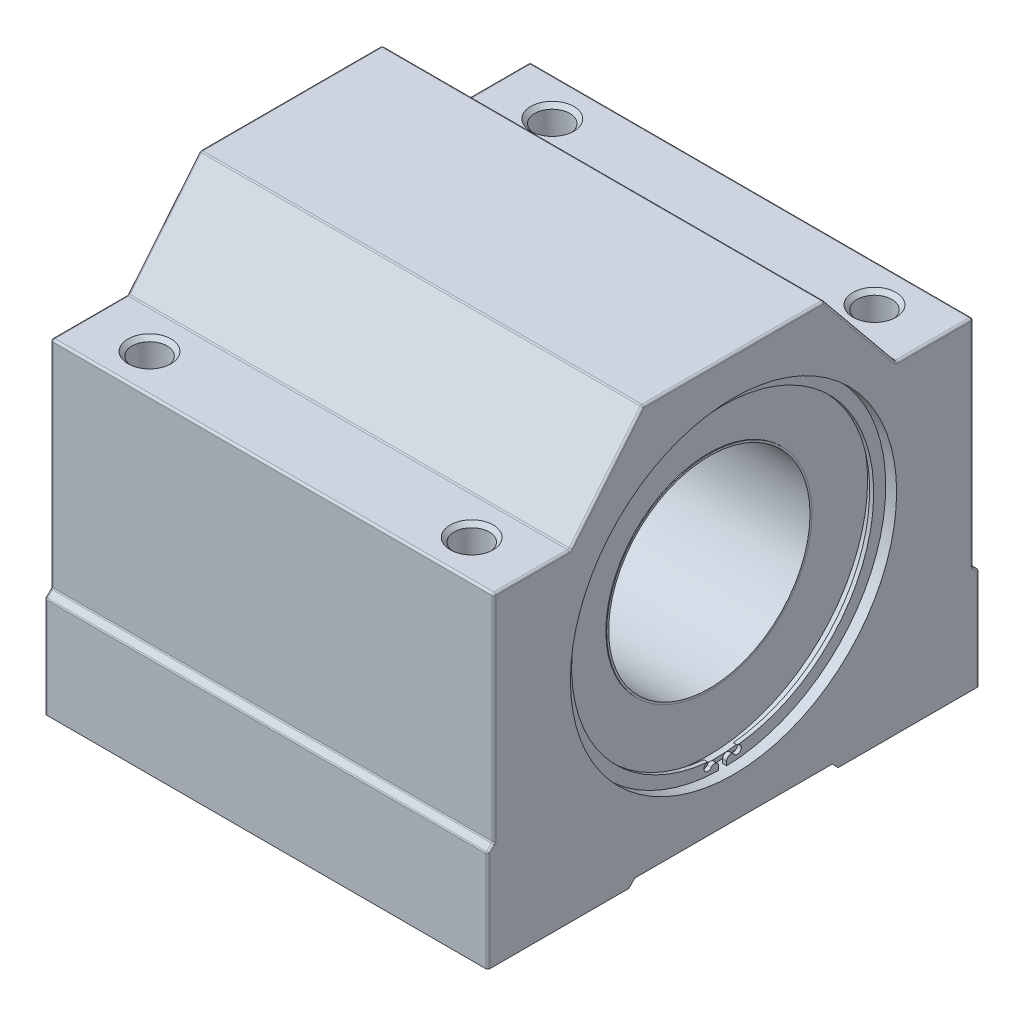
SolidWorks part; units mm, degrees
ref_plane "Front Plane" through (0, 0, 0) normal (0, 0, 1) x (1, 0, 0)
ref_plane "Top Plane" through (0, 0, 0) normal (0, 1, 0) x (1, 0, 0)
ref_plane "Right Plane" through (0, 0, 0) normal (1, 0, 0) x (0, 0, -1)
sketch "Sketch1" plane through (0, 0, 0) normal (1, 0, 0) x (0, 0, -1)
  line L1 (-26, -52) -> (-24.5, -50.5)
  line L2 (-24.5, -50.5) -> (24.5, -50.5)
  line L3 (24.5, -50.5) -> (26, -52)
  line L4 (26, -52) -> (61, -52)
  line L6 (61, -27) -> (59.5, -25.5)
  line L8 (59.5, 28) -> (40.5, 28)
  line L9 (40.5, 28) -> (22.5, 50)
  line L10 (22.5, 50) -> (-22.5, 50)
  line L11 (-22.5, 50) -> (-40.5, 28)
  line L12 (-40.5, 28) -> (-59.5, 28)
  line L15 (-61, -27) -> (-61, -52)
  line L16 (0, -50.5) -> (0, 50) construction
  line L17 (-16.278, 0) -> (14.0247, 0) construction
  line L18 (-61, -52) -> (-26, -52)
  line L19 (61, -27) -> (61, -52)
  line L20 (-59.5, -25.5) -> (-59.5, 28)
  line L21 (59.5, -25.5) -> (59.5, 28)
  line L22 (-50, 28) -> (-50, -52) construction
  line L23 (-50, -52) -> (50, 28) construction
  line L24 (50, 28) -> (50, -52) construction
  line L25 (-61, -27) -> (-59.5, -25.5)
  line L26 (-40.5, 0) -> (40.5, 0) construction
  circle A0 centre (0, 0) radius 40.5
  circle A1 centre (0, 0) radius 39.5
  circle A2 centre (0, 0) radius 25
  point P18 (0, 50)
  dimension "D12" = 50
  dimension "D1" = 122
  dimension "D2" = 80
  dimension "D3" = 52
  dimension "D5" = 102
  dimension "D6" = 100
  dimension "D4" = 25
  dimension "D7" = 1.5
  dimension "D8" = 45
  dimension "D9" = 1.5
  dimension "D10" = 35
  dimension "D11" = 1
extrude "Boss-Extrude1" add sketch "Sketch1" along normal blind 110 contours L25 L15 L18 L1 L2 L3 L4 L19 L6 L21 L8 L9 L10 L11 L12 L20 A0 region at (0, -50.4098, 43.5)
extrude "Extrude-Thin1" add sketch "Sketch1<4>" along normal blind 103.5 from offset 0.5 separate body thin contours A2 thin type one direction wall 0.5
sketch "Sketch1<4>" plane through (0, 0, 0) normal (1, 0, 0) x (0, 0, -1) same geometry as "Sketch1"
extrude "Boss-Extrude2" add sketch "Sketch1<5>" along normal blind 103 from offset 0.8 contours A1 A2 region at (0, 0, 38.3828)
sketch "Sketch1<5>" plane through (0, 0, 0) normal (1, 0, 0) x (0, 0, -1) same geometry as "Sketch1"
extrude "Boss-Extrude3" add sketch "Sketch1<6>" along normal blind 105 from offset 0.3 contours A0 A1 region at (0, 0, 40.3854)
sketch "Sketch1<6>" plane through (0, 0, 0) normal (1, 0, 0) x (0, 0, -1) same geometry as "Sketch1"
ref_plane "Plane1" through (105.3, 0, 0) normal (1, 0, 0) x (0, 0, -1)
sketch "Sketch3" plane through (105.3, 0, 0) normal (1, 0, 0) x (0, 0, -1)
  line L0 (0, 0) -> (0, -50000) construction
  line L1 (-1.0007, -39.4873) -> (-1.0261, -40.487)
  line L2 (1.0007, -39.4873) -> (1.0261, -40.487)
  circle A0 centre (0, 0) radius 40.5 construction
  arc A1 (1.0261, -40.487) -> (-1.0261, -40.487) centre (0, 0) ccw
  circle A2 centre (0, 0) radius 39.5 construction
  arc A3 (0, -39.5) -> (1.0007, -39.4873) centre (0, 0) ccw
  arc A4 (-1.0007, -39.4873) -> (-2.8274, -38.8877) centre (-2, -39.4493) ccw
  circle A5 centre (-2, -39.4493) radius 0.25
  arc A6 (-2.2496, -39.4359) -> (-1.7503, -39.4612) centre (0, 0) ccw
  arc A7 (-2.8274, -38.8877) -> (-3.6518, -37.3261) centre (-3.6548, -38.3261) cw
  arc A8 (2.8274, -38.8877) -> (3.6518, -37.3261) centre (3.6548, -38.3261) ccw
  circle A10 centre (2, -39.4493) radius 0.25
  arc A11 (1.0007, -39.4873) -> (2.8274, -38.8877) centre (2, -39.4493) cw
  arc A13 (3.6518, -37.3261) -> (-3.6518, -37.3261) centre (0, 0) ccw
  dimension "D1" = 0.5
  dimension "D2" = 2
  dimension "D3" = 1
  dimension "D4" = 2
extrude "Boss-Extrude4" add sketch "Sketch3" along normal blind 1 from offset 1 contours A11 A8 A13 A7 A4 L1 A1 L2
fillet "Fillet1" radius 0.5 32 edges at (55, -25.5, -59.5) (55, -25.5, 59.5) (55, -27, 61) (55, -27, -61) (55, 28, -40.5) (55, 28, 40.5) (55, 50, 22.5) (55, 50, -22.5) (55, 28, -59.5) (55, 28, 59.5) (110, 39, -31.5) (110, 39, 31.5) (110, 1.25, 59.5) (0, -26.25, 60.25) (0, 39, 31.5) (110, -26.25, -60.25) (110, -39.5, -61) (110, 1.25, -59.5) (110, 50, 0) (110, 28, -50) (110, 28, 50) (110, -26.25, 60.25) (110, -39.5, 61) (0, -39.5, -61) (0, -26.25, -60.25) (0, 1.25, -59.5) (0, 39, -31.5) (0, 28, -50) (0, 50, 0) (0, -39.5, 61) (0, 1.25, 59.5) (0, 28, 50)
sketch "Sketch4" plane through (0, -52, 0) normal (0, -1, 0) x (1, 0, 0)
  line L0 (55, 61) -> (55, -61) construction
  line L1 (109.5, 61) -> (0.5, 61) construction
  line L2 (109.5, -61) -> (0.5, -61) construction
  line L4 (-4.9444, 50) -> (27.0918, 50) construction
  line L6 (0, 0) -> (36.1646, 0) construction
  circle A0 centre (15, 50) radius 4.35
  circle A1 centre (95, 50) radius 4.35
  circle A2 centre (95, -50) radius 4.35
  circle A3 centre (15, -50) radius 4.35
  dimension "D2" = 8.7
  dimension "D1" = 50
  dimension "D3" = 80
extrude "Cut-Extrude3" cut sketch "Sketch4" against normal through all
chamfer "Chamfer1" distance 1 angle 45 6 edges at (95, 28, -54.35) (15, 28, -54.35) (15, 28, 45.65) (95, 28, 45.65) (95, -52, 54.35) (15, -52, 45.65)
equation "\"D1@Boss-Extrude2\"= \"D1@Boss-Extrude1\" - 2 - 5"
equation "\"D1@Boss-Extrude3\"= \"D1@Boss-Extrude1\" - 5"
equation "\"D1@Sketch4\"= \"D6@Sketch1\" / 2"
equation "\"D1@Extrude-Thin1\"= \"D1@Boss-Extrude3\" - 1.5"
